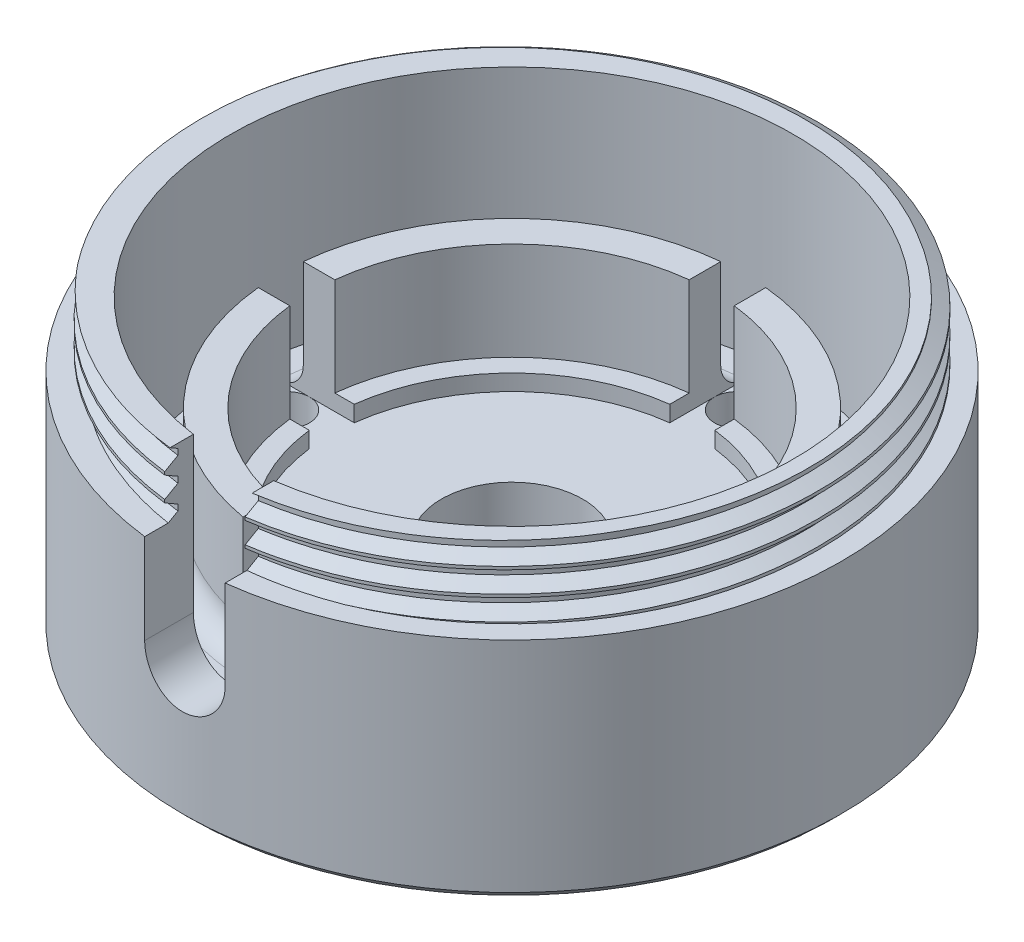
SolidWorks part; units mm, degrees
ref_plane "Front plane" through (0, 0, 0) normal (0, 0, 1) x (1, 0, 0)
ref_plane "Top plane" through (0, 0, 0) normal (0, 1, 0) x (1, 0, 0)
ref_plane "Right plane" through (0, 0, 0) normal (1, 0, 0) x (0, 0, -1)
ref_axis "Axis X" through (0, 0, 0) along (1, 0, 0)
ref_axis "Axis Y" through (0, 0, 0) along (0, 1, 0)
ref_axis "Axis Z" through (0, 0, 0) along (0, 0, 1)
sketch "Sketch1" plane through (0, 0, 0) normal (0, 1, 0) x (1, 0, 0)
  circle A0 centre (0, 0) radius 20.5
  circle A1 centre (0, 0) radius 4.4
  circle A2 centre (0, 0) radius 14 construction
  circle A3 centre (0, 14) radius 1.4
  circle A4 centre (14, 0) radius 1.4
  circle A5 centre (0, -14) radius 1.4
  circle A6 centre (-14, 0) radius 1.4
  point P16 (0, 0)
  dimension "D1" = 41
  dimension "D2" = 8.8
  dimension "D3" = 28
  dimension "D4" = 2.8
  dimension "D5" = 4
extrude "Extrude1" add sketch "Sketch1" along normal blind 5
sketch "Sketch2" plane through (0, 5, 0) normal (0, 1, 0) x (1, 0, 0)
  line L0 (-1.4, 14.382) -> (-1.4, 11.2129)
  line L2 (1.4, 14.382) -> (1.4, 11.2129)
  line L4 (14.382, -1.4) -> (11.2129, -1.4)
  line L5 (14.382, 1.4) -> (11.2129, 1.4)
  line L6 (-1.4, -14.382) -> (-1.4, -11.2129)
  line L7 (1.4, -14.382) -> (1.4, -11.2129)
  line L8 (-14.382, 1.4) -> (-11.2129, 1.4)
  line L9 (-14.382, -1.4) -> (-11.2129, -1.4)
  arc A8 (-1.4, 11.2129) -> (-11.2129, 1.4) centre (0, 0) ccw
  arc A9 (-1.4, 14.382) -> (-14.382, 1.4) centre (0, 0) ccw
  circle A10 centre (0, 14) radius 1.4 construction
  circle A11 centre (14, 0) radius 1.4 construction
  arc A12 (11.2129, 1.4) -> (1.4, 11.2129) centre (0, 0) ccw
  arc A13 (14.382, 1.4) -> (1.4, 14.382) centre (0, 0) ccw
  arc A14 (1.4, -11.2129) -> (11.2129, -1.4) centre (0, 0) ccw
  arc A15 (1.4, -14.382) -> (14.382, -1.4) centre (0, 0) ccw
  arc A16 (-14.382, -1.4) -> (-1.4, -14.382) centre (0, 0) ccw
  arc A17 (-11.2129, -1.4) -> (-1.4, -11.2129) centre (0, 0) ccw
  point P24 (0, 0)
  dimension "D1" = 22.6
  dimension "D2" = 28.9
  dimension "D3" = 4
extrude "Extrude2" add sketch "Sketch2" along normal blind 7.1
sketch "Sketch7" plane through (0, 12.1, 0) normal (0, 1, 0) x (1, 0, 0)
  circle A0 centre (0, 0) radius 12.5
  dimension "D1" = 25
extrude "Extrude5" cut sketch "Sketch7" against normal offset from surface (6.1 mm away) 1 up to face at (0, 5, 4.4)
fillet "Fillet1" radius 1.5 4 edges at (-10.2177, 5, -10.2177) (10.2177, 5, -10.2177) (10.2177, 5, 10.2177) (-10.2177, 5, 10.2177)
sketch "Sketch8" plane through (0, 5, 0) normal (0, 1, 0) x (1, 0, 0)
  circle A0 centre (0, 0) radius 20.5
  circle A1 centre (0, 0) radius 17.5
  circle A2 centre (0, 0) radius 20.5 construction
  dimension "D1" = 35
extrude "Extrude6" add sketch "Sketch8" along normal blind 9.1
sketch "Sketch4" plane through (0, 14.1, 0) normal (0, 1, 0) x (1, 0, 0)
  circle A0 centre (0, 0) radius 17.5
  circle A1 centre (0, 0) radius 18.45
  dimension "D1" = 35
  dimension "D2" = 0.95
extrude "Extrude4" add sketch "Sketch4" along normal blind 4
thread "Thread1" pitch 1.5 method extrude trim with start face yes trim with end face yes profile "Sketch6" start angle 0, offset 2, length 0, pitch 1.5, diameter 36.9
ref_plane "Plane1" through (-18.45, 20.1, 0) normal (0, 0, 1) x (-1, 0, 0)
sketch "Sketch6" plane through (-18.45, 20.1, 0) normal (0, 0, 1) x (-1, 0, 0)
  line L0 (0, 0) -> (0, 1.5) construction
  line L1 (0, 0) -> (0.8119, 0.4687)
  line L2 (0.8119, 0.4687) -> (0.8119, 0.6562)
  line L3 (0.8119, 0.6562) -> (0, 1.125)
  line L4 (0.8119, 0.5625) -> (0, 0.5625) construction
  line L11 (0, 0) -> (0, 1.125)
  point P2 (0, 0)
  dimension "Pitch" = 1.5
  dimension "Profile_Angle" = 60
  dimension "Profile_Land" = 0.1875
  dimension "Profile_Height" = 0.8119
chamfer "Chamfer2" distance 1.5 angle 45 1 edges at (0, 0, 4.4)
chamfer "Chamfer3" distance 0.5 angle 45 1 edges at (0, 0, 20.5)
chamfer "Chamfer4" distance 1 angle 45 4 edges at (0, 0, -12.6) (14, 0, 1.4) (-14, 0, 1.4) (0, 0, 15.4)
sketch "Sketch9" plane through (0, 0, 0) normal (0, 0, 1) x (1, 0, 0)
  line L0 (-1.4, 6) -> (-11.2129, 6) construction
  line L1 (-2.5, 8.5) -> (-2.5, 19.1)
  line L2 (-2.5, 19.1) -> (2.5, 19.1)
  line L3 (2.5, 19.1) -> (2.5, 8.5)
  line L4 (17.5, 18.1) -> (-17.5, 18.1) construction
  arc A0 (-2.5, 8.5) -> (2.5, 8.5) centre (0, 8.5) ccw
  dimension "D2" = 5
  dimension "D1" = 2.5
  dimension "D3" = 1
extrude "Extrude7" cut sketch "Sketch9" along normal through all
equation "\"motor_D\"= 30'Motor diameter"
equation "\"motor_H\"= 13'Motor heigh"
equation "\"motor_d1\"= 25.4558'Seating diameter of screws on the fixed part of the motor"
equation "\"motor_s1\"= 2'Screws diameter on the fixed part of motor"
equation "\"motor_a2\"= 10'Seating parameter in rectangle of screws on the moving part of the motor"
equation "\"motor_s2\"= 2'Screws diameter on the moving part of motor"
equation "\"motor_Dc\"= 5'Central hole diameter of motor"
equation "\"bearing_d1\"= 6'Bearing inner diameter"
equation "\"bearing_d2\"= 17'Bearing external diameter"
equation "\"bearing h\"= 6'Bearing heigh"
equation "\"pin_d\"= 2'Pin diameter"
equation "\"pin_h\"= 12'Pin heigh"
equation "\"magnet_d1\"= 5'Magnet inner diameter"
equation "\"magnet_d2\"= 9.5'Magnet external diameter"
equation "\"magnet_h\"= 3'Magnet heigh"
equation "\"motor_b2\"= 22'Seating parameter in rectangle of screws on the moving part of the motor"
equation "\"motor_d2\"= 0'Seating diameter of screws on the moving part of the motor (if this parameter is not determine, write 0)"
equation "\"motor_cmd\"= 12'Central magnet mount diameter"
equation "\"motor_cmh\"= 1.4'Central magnet mount heigh (if not write 0)"
equation "\"motor_whR\"= 10'Distance from center of motor to wires"
equation "\"D1@Sketch1\" = IIF ( \"motor_D\" < 34 , 41 , \"motor_D\" + 8 )"
equation "\"D2@Sketch1\"=\"ft_sensor_d1\"-1"
equation "\"D4@Sketch1\"=3-\"print_offset\""
equation "\"D1@Extrude2\"=\"ft_sensor_h\""
equation "\"D1@Sketch4\" = IIF ( \"motor_D\" < 34 , 41 , \"motor_D\" + 8 ) - 6"
equation "\"print_offset\"= 0.2'Offset for printing holes"
equation "\"D2@Sketch4\"=0.95"
equation "\"ft_sensor_d1\"= 9.8"
equation "\"ft_sensor_d2\"= 24.9"
equation "\"ft_sensor_d3\"= 22.6'Inner diameter of "
equation "\"ft_sensor_h\"= 7.1"
equation "\"ft_sensor_whD\" = 5"
equation "\"D1@Sketch2\"=\"ft_sensor_d3\""
equation "\"D2@Sketch2\"=\"ft_sensor_d2\"+4"
equation "\"D1@Sketch7\"=\"ft_sensor_d2\"+\"print_offset\"/2"
equation "\"D1@Sketch8\" = IIF ( \"motor_D\" < 34 , 41 , \"motor_D\" + 8 ) - 6"
equation "\"D1@Extrude6\"=\"ft_sensor_h\"+1+1"
equation "\"D1@Sketch9\"=\"ft_sensor_whD\"/2"
equation "\"D2@Sketch9\"=\"ft_sensor_whD\""
